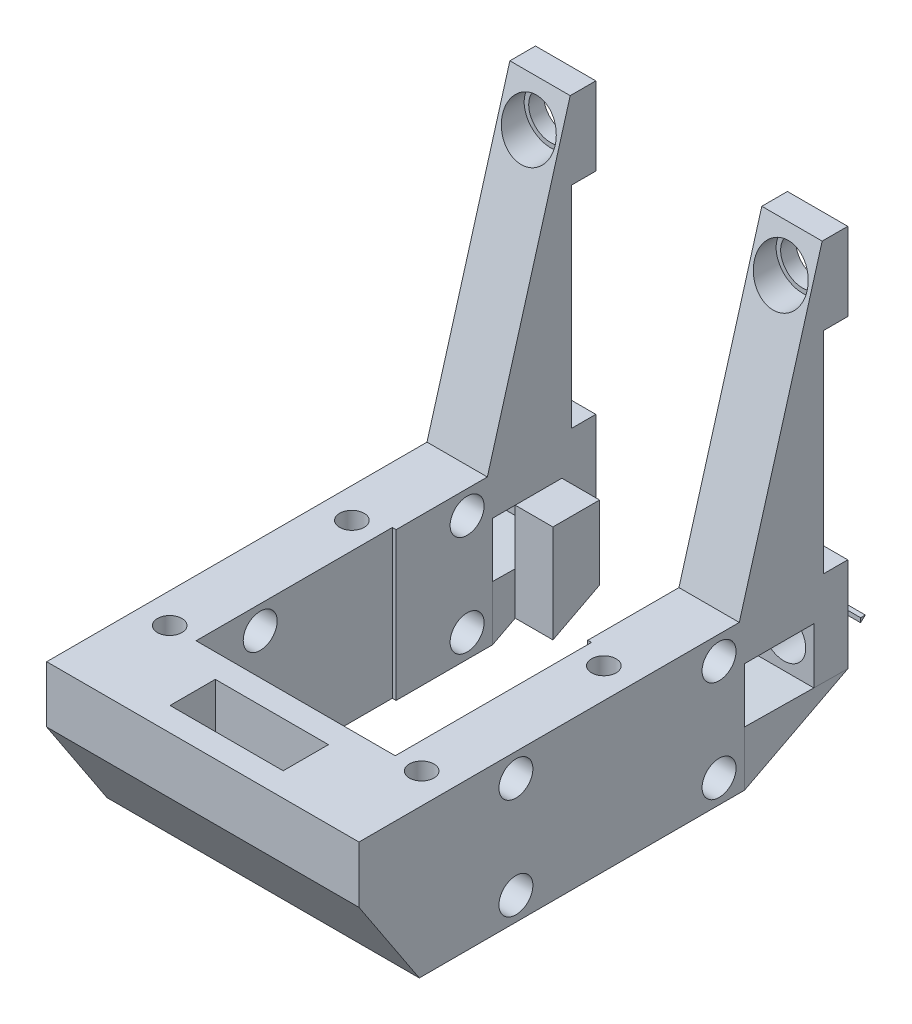
SolidWorks part; units mm, degrees
ref_plane "Front Plane" through (0, 0, 0) normal (0, 0, 1) x (1, 0, 0)
ref_plane "Top Plane" through (0, 0, 0) normal (0, 1, 0) x (1, 0, 0)
ref_plane "Right Plane" through (0, 0, 0) normal (1, 0, 0) x (0, 0, -1)
sketch "Sketch1" plane through (-474.147, -1016.1135, 5527.2949) normal (0, 0, 1) x (1, 0, 0)
  line L1 (211.6017, 683.0822) -> (219.1017, 683.0822)
  line L2 (211.6017, 683.0822) -> (211.6017, 675.5822)
  line L3 (211.6017, 675.5822) -> (219.1017, 675.5822)
  line L4 (219.1017, 683.0822) -> (219.1017, 675.5822)
  line L6 (237.0017, 683.0822) -> (237.0017, 675.5822)
  line L7 (237.0017, 675.5822) -> (229.5017, 675.5822)
  line L8 (229.5017, 683.0822) -> (229.5017, 675.5822)
  line L9 (237.0017, 683.0822) -> (229.5017, 683.0822)
  line L10 (237.0017, 718.5082) -> (229.5017, 718.5082)
  line L11 (237.0017, 711.0082) -> (237.0017, 718.5082)
  line L12 (229.5017, 711.0082) -> (229.5017, 718.5082)
  line L13 (237.0017, 711.0082) -> (229.5017, 711.0082)
  line L14 (211.6017, 718.5082) -> (219.1017, 718.5082)
  line L15 (211.6017, 711.0082) -> (211.6017, 718.5082)
  line L16 (219.1017, 711.0082) -> (219.1017, 718.5082)
  line L17 (211.6017, 711.0082) -> (219.1017, 711.0082)
  line L18 (219.1017, 675.5822) -> (229.5017, 675.5822) construction
  line L20 (237.0017, 683.0822) -> (237.0017, 711.0082) construction
  line L22 (211.6017, 683.0822) -> (211.6017, 711.0082) construction
  line L24 (219.1017, 718.5082) -> (229.5017, 718.5082) construction
  dimension "D1" = 237.1453
  dimension "D2" = 244.6453
  dimension "D3" = 255.0453
  dimension "D4" = 297.6053
  dimension "D5" = 333.0313
extrude "Boss-Extrude1" add sketch "Sketch1" along normal blind 5.5
sketch "Sketch2" plane through (0, 0, 5532.7949) normal (0, 0, 1) x (1, 0, 0)
  line L0 (-229.1453, -333.0313) -> (-229.1453, -340.5313)
  line L1 (-262.5453, -333.0313) -> (-270.5453, -333.0313)
  line L2 (-262.5453, -333.0313) -> (-262.5453, -340.5313)
  line L3 (-262.5453, -340.5313) -> (-270.5453, -340.5313)
  line L4 (-270.5453, -333.0313) -> (-270.5453, -340.5313)
  line L5 (-262.5453, -333.0313) -> (-262.5453, -340.5313) construction
  line L6 (-262.5453, -340.5313) -> (-255.0453, -340.5313) construction
  line L7 (-249.8453, -297.6053) -> (-249.8453, -340.5313) construction
  line L8 (-262.5453, -319.0683) -> (-237.1453, -319.0683) construction
  line L9 (-237.1453, -340.5313) -> (-229.1453, -340.5313)
  line L10 (-237.1453, -333.0313) -> (-237.1453, -340.5313)
  line L11 (-237.1453, -333.0313) -> (-229.1453, -333.0313)
  dimension "D1" = 7.5
  dimension "D2" = 8
  dimension "D3" = 12.7
  dimension "D4" = 21.463
extrude "Boss-Extrude2" add sketch "Sketch2" along normal blind 45 and the other way blind 5.5
sketch "Sketch3" plane through (0, 0, 5577.7949) normal (0, 0, 1) x (1, 0, 0)
  line L0 (-237.1453, -340.5313) -> (-229.1453, -340.5313) construction
  line L1 (-270.5453, -333.0313) -> (-229.1453, -333.0313)
  line L2 (-270.5453, -333.0313) -> (-270.5453, -340.5313)
  line L3 (-270.5453, -340.5313) -> (-229.1453, -340.5313)
  line L4 (-229.1453, -333.0313) -> (-229.1453, -340.5313)
  line L5 (-229.1453, -340.5313) -> (-229.1453, -333.0313) construction
extrude "Boss-Extrude3" add sketch "Sketch3" along normal blind 16
sketch "Sketch4" plane through (-262.5453, 0, 0) normal (-1, 0, 0) x (0, 0, 1)
  line L3 (5527.2949, -333.0313) -> (5527.2949, -294.744)
  line L4 (5527.2949, -294.744) -> (5532.3941, -294.744)
  line L5 (5527.2949, -297.6053) -> (5527.2949, -305.1053) construction
  line L6 (5532.3941, -294.744) -> (5543.3789, -333.0313)
  line L7 (5543.3789, -333.0313) -> (5527.2949, -333.0313)
  line L8 (5543.3789, -333.0313) -> (5581.4885, -333.0313) construction
extrude "Boss-Extrude4" add sketch "Sketch4" along normal blind 8
ref_plane "Plane1" through (-249.8453, 0, 0) normal (-1, 0, 0) x (0, 0, 1)
mirror "Mirror1" about plane through (-249.8453, 0, 0) normal (-1, 0, 0) of "Boss-Extrude2", "Boss-Extrude4"
sketch "Sketch5" plane through (0, 0, 5532.7949) normal (0, 0, 1) x (1, 0, 0)
  line L0 (-258.7953, -297.6053) -> (-258.7953, -305.1053) construction
  line L1 (-255.0453, -297.6053) -> (-262.5453, -297.6053) construction
  line L2 (-262.5453, -305.1053) -> (-255.0453, -305.1053) construction
  line L3 (-255.0453, -301.3553) -> (-262.5453, -301.3553) construction
  line L4 (-255.0453, -305.1053) -> (-255.0453, -297.6053) construction
  line L5 (-262.5453, -297.6053) -> (-262.5453, -305.1053) construction
  line L6 (-255.0453, -297.6053) -> (-244.6453, -297.6053) construction
  line L7 (-249.8453, -297.6053) -> (-249.8453, -305.1053) construction
  line L8 (-255.0453, -305.1053) -> (-244.6453, -305.1053) construction
  line L9 (-255.0453, -340.5313) -> (-244.6453, -340.5313) construction
  line L10 (-255.0453, -333.0313) -> (-244.6453, -333.0313) construction
  line L11 (-249.8453, -305.1053) -> (-249.8453, -333.0313) construction
  line L12 (-255.0453, -333.0313) -> (-255.0453, -305.1053) construction
  line L13 (-249.8453, -319.0683) -> (-255.0453, -319.0683) construction
  line L14 (-244.6453, -301.3553) -> (-237.1453, -301.3553) construction
  line L15 (-240.8953, -297.6053) -> (-240.8953, -305.1053) construction
  line L16 (-244.6453, -336.7813) -> (-237.1453, -336.7813) construction
  line L17 (-240.8953, -340.5313) -> (-240.8953, -333.0313) construction
  line L18 (-258.7953, -340.5313) -> (-258.7953, -333.0313) construction
  line L19 (-255.0453, -336.7813) -> (-262.5453, -336.7813) construction
  circle A0 centre (-258.7953, -301.3553) radius 2.5
  circle A1 centre (-240.8953, -301.3553) radius 2.5
  circle A2 centre (-240.8953, -336.7813) radius 2.5
  circle A3 centre (-258.7953, -336.7813) radius 2.5
  dimension "D1" = 5
extrude "Cut-Extrude1" cut sketch "Sketch5" against normal blind 8
sketch "Sketch6" plane through (-270.5453, 0, 0) normal (-1, 0, 0) x (0, 0, 1)
  line L0 (5527.2949, -340.5313) -> (5593.7949, -340.5313) construction
  line L1 (5539.6853, -340.5313) -> (5577.7949, -340.5313)
  line L2 (5539.6853, -340.5313) -> (5539.6853, -352.6436)
  line L3 (5539.6853, -352.6436) -> (5577.7949, -352.6436)
  line L4 (5577.7949, -340.5313) -> (5577.7949, -352.6436)
extrude "Boss-Extrude6" add sketch "Sketch6" against normal blind 8
ref_plane "Plane2" through (-249.8453, 0, 0) normal (-1, 0, 0) x (0, 0, 1)
mirror "Mirror2" about plane through (-249.8453, 0, 0) normal (-1, 0, 0) of "Boss-Extrude6"
sketch "Sketch9" plane through (0, 0, 5577.7949) normal (0, 0, 1) x (1, 0, 0)
  line L0 (-262.5453, -352.6436) -> (-270.5453, -352.6436) construction
  line L1 (-270.5453, -352.6436) -> (-229.1453, -352.6436)
  line L2 (-270.5453, -352.6436) -> (-270.5453, -340.5313)
  line L3 (-270.5453, -340.5313) -> (-229.1453, -340.5313)
  line L4 (-229.1453, -352.6436) -> (-229.1453, -340.5313)
  line L5 (-270.5453, -352.6436) -> (-270.5453, -340.5313) construction
  line L6 (-270.5453, -340.5313) -> (-229.1453, -340.5313) construction
extrude "Boss-Extrude7" add sketch "Sketch9" along normal blind 8
sketch "Sketch10" plane through (-270.5453, 0, 0) normal (-1, 0, 0) x (0, 0, 1)
  line L0 (5572.9896, -336.1377) -> (5572.9896, -333.0313) construction
  line L1 (5543.3789, -333.0313) -> (5593.7949, -333.0313) construction
  line L2 (5572.9896, -352.6436) -> (5572.9896, -349.5373) construction
  line L3 (5539.6853, -352.6436) -> (5585.7949, -352.6436) construction
  circle A4 centre (5546.0612, -349.5373) radius 2.25
  circle A5 centre (5572.9896, -349.5373) radius 2.25
  circle A6 centre (5546.0612, -336.1377) radius 2.25
  circle A7 centre (5572.9896, -336.1377) radius 2.25
  dimension "D1" = 4.5
  dimension "D2" = 13.6671
  dimension "D3" = 40.5955
  dimension "D4" = 3.1064
extrude "Cut-Extrude2" cut sketch "Sketch10" against normal through all
sketch "Sketch11" plane through (-270.5453, 0, 0) normal (-1, 0, 0) x (0, 0, 1)
  line L0 (5527.2949, -340.3725) -> (5539.6853, -352.6436)
  line L1 (5527.2949, -294.744) -> (5527.2949, -340.5313) construction
  line L2 (5539.6853, -340.5313) -> (5539.6853, -352.6436) construction
  line L3 (5539.6853, -352.6436) -> (5539.6853, -340.5313)
  line L4 (5527.2949, -340.5313) -> (5539.6853, -340.5313) construction
  line L5 (5539.6853, -340.5313) -> (5527.2949, -340.3725)
  line L7 (5539.6853, -352.6436) -> (5585.7949, -352.6436) construction
  dimension "D1" = 12.2712
extrude "Boss-Extrude8" add sketch "Sketch11" against normal blind 8
sketch "Sketch12" plane through (-229.1453, 0, 0) normal (1, 0, 0) x (0, 0, -1)
  line L0 (-5539.6853, -352.6436) -> (-5526.672, -340.5313)
  line L1 (-5539.6853, -340.5313) -> (-5539.6853, -352.6436) construction
  line L2 (-5539.6853, -340.5313) -> (-5527.2949, -340.5313) construction
  line L3 (-5526.672, -340.5313) -> (-5539.6853, -340.5313)
  line L4 (-5539.6853, -340.5313) -> (-5539.6853, -352.6436)
  line L5 (-5526.672, -340.341) -> (-5526.672, -300.7017) construction
extrude "Boss-Extrude9" add sketch "Sketch12" against normal blind 8
sketch "Sketch13" plane through (-270.5453, 0, 0) normal (-1, 0, 0) x (0, 0, 1)
  line L0 (5527.8316, -294.744) -> (5527.8316, -302.244) construction
  line L1 (5532.3941, -294.744) -> (5527.2949, -294.744) construction
  line L2 (5527.8316, -340.5313) -> (5527.8316, -333.0313) construction
  line L3 (5527.2949, -294.744) -> (5527.2949, -340.5313) construction
  line L4 (5527.2949, -333.0313) -> (5532.2204, -333.0313)
  line L5 (5527.2949, -333.0313) -> (5527.2949, -305.1053)
  line L6 (5527.2949, -305.1053) -> (5532.2204, -305.1053)
  line L7 (5532.2204, -333.0313) -> (5532.2204, -305.1053)
  dimension "D1" = 7.5
  dimension "D2" = 7.5
extrude "Cut-Extrude3" cut sketch "Sketch13" against normal through all
sketch "Sketch14" plane through (-270.5453, 0, 0) normal (-1, 0, 0) x (0, 0, 1)
  line L0 (5585.7949, -352.6436) -> (5593.7949, -340.5313)
  line L1 (5585.7949, -340.5313) -> (5585.7949, -352.6436) construction
  line L2 (5585.7949, -340.5313) -> (5593.7949, -340.5313) construction
  line L3 (5593.7949, -340.5313) -> (5585.7949, -340.5313)
  line L4 (5585.7949, -340.5313) -> (5585.7949, -352.6436)
extrude "Boss-Extrude10" add sketch "Sketch14" against normal blind 41.4
sketch "Sketch16" plane through (0, -333.0313, 0) normal (0, 1, 0) x (1, 0, 0)
  line L1 (-263.0453, -5555.4748) -> (-236.6453, -5555.4748)
  line L2 (-263.0453, -5555.4748) -> (-263.0453, -5581.4885)
  line L3 (-263.0453, -5581.4885) -> (-236.6453, -5581.4885)
  line L4 (-236.6453, -5555.4748) -> (-236.6453, -5581.4885)
  line L5 (-263.0453, -5566.5853) -> (-270.5453, -5566.5853) construction
  line L6 (-270.5453, -5543.3789) -> (-270.5453, -5593.7949) construction
  line L7 (-236.6453, -5567.7425) -> (-229.1453, -5567.7425) construction
  line L8 (-229.1453, -5593.7949) -> (-229.1453, -5543.3789) construction
  line L10 (-229.1453, -5543.3789) -> (-237.1453, -5543.3789) construction
  dimension "D1" = 7.5
  dimension "D2" = 12.0959
  dimension "D3" = 23.2064
  dimension "D4" = 24.3636
  dimension "D5" = 38.1096
extrude "Cut-Extrude5" cut sketch "Sketch16" against normal through all
sketch "Sketch17" plane through (0, -297.6053, 0) normal (0, 1, 0) x (1, 0, 0)
  line L1 (-237.1453, -5527.2949) -> (-262.5453, -5527.2949)
  line L2 (-237.1453, -5527.2949) -> (-237.1453, -5532.7949)
  line L3 (-237.1453, -5532.7949) -> (-262.5453, -5532.7949)
  line L4 (-262.5453, -5527.2949) -> (-262.5453, -5532.7949)
extrude "Cut-Extrude6" cut sketch "Sketch17" against normal blind 50
sketch "Sketch18" plane through (0, -294.744, 0) normal (0, 1, 0) x (1, 0, 0)
  line L1 (-270.5453, -5527.2949) -> (-229.1453, -5527.2949)
  line L2 (-270.5453, -5527.2949) -> (-270.5453, -5528.9982)
  line L3 (-270.5453, -5528.9982) -> (-229.1453, -5528.9982)
  line L4 (-229.1453, -5527.2949) -> (-229.1453, -5528.9982)
  line L5 (-229.1453, -5532.3941) -> (-229.1453, -5527.2949) construction
extrude "Cut-Extrude7" cut sketch "Sketch18" against normal blind 50
sketch "Sketch19" plane through (0, 0, 5528.9982) normal (0, 0, -1) x (-1, 0, 0)
  line L0 (233.1453, -294.744) -> (233.1453, -305.1053) construction
  line L1 (237.1453, -294.744) -> (229.1453, -294.744) construction
  line L2 (237.1453, -305.1053) -> (229.1453, -305.1053) construction
  line L3 (229.1453, -299.9246) -> (237.1453, -299.9246) construction
  line L4 (229.1453, -305.1053) -> (229.1453, -294.744) construction
  line L5 (237.1453, -305.1053) -> (237.1453, -294.744) construction
  circle A0 centre (233.1453, -299.9246) radius 2.9
  dimension "D1" = 5.8
extrude "Cut-Extrude8" cut sketch "Sketch19" against normal blind 50
ref_plane "Plane3" through (0, 0, 5538.9982) normal (0, 0, -1) x (-1, 0, 0)
sketch "Sketch20" plane through (0, 0, 5538.9982) normal (0, 0, -1) x (-1, 0, 0)
  circle A1 centre (233.1453, -299.9246) radius 3.5
  dimension "D1" = 7
extrude "Cut-Extrude9" cut sketch "Sketch20" along normal blind 8
ref_plane "Plane4" through (-249.8453, 0, 0) normal (-1, 0, 0) x (0, 0, 1)
mirror "Mirror3" about plane through (-249.8453, 0, 0) normal (-1, 0, 0) of "Cut-Extrude9", "Cut-Extrude8"
ref_plane "Plane5" through (0, -319.0683, 0) normal (0, 1, 0) x (1, 0, 0)
sketch "Sketch21" plane through (-270.5453, 0, 0) normal (-1, 0, 0) x (0, 0, 1)
  line L0 (5528.9982, -342.0594) -> (5528.9982, -333.0313) construction
  line L1 (5528.9982, -338.1154) -> (5539.6853, -338.1154)
  line L2 (5528.9982, -338.1154) -> (5528.9982, -352.6436)
  line L3 (5528.9982, -352.6436) -> (5539.6853, -352.6436)
  line L4 (5539.6853, -338.1154) -> (5539.6853, -352.6436)
extrude "Cut-Extrude10" cut sketch "Sketch21" against normal blind 55
sketch "Sketch22" plane through (0, -338.1154, 0) normal (0, -1, 0) x (1, 0, 0)
  line L0 (-262.5453, 5528.9982) -> (-262.5453, 5539.6853) construction
  line L1 (-270.5453, 5528.9982) -> (-262.5453, 5528.9982)
  line L2 (-270.5453, 5528.9982) -> (-270.5453, 5533.4982)
  line L3 (-270.5453, 5533.4982) -> (-262.5453, 5533.4982)
  line L4 (-262.5453, 5528.9982) -> (-262.5453, 5533.4982)
  dimension "D1" = 4.5
extrude "Boss-Extrude11" add sketch "Sketch22" along normal blind 7.4279
mirror "Mirror5" about plane through (-249.8453, 0, 0) normal (-1, 0, 0) of "Boss-Extrude11"
sketch "Sketch23" plane through (0, 0, 5528.9982) normal (0, 0, -1) x (-1, 0, 0)
  circle A0 centre (233.1189, -341.4699) radius 2.9
  dimension "D1" = 5.8
extrude "Cut-Extrude11" cut sketch "Sketch23" against normal blind 5
ref_plane "Plane6" through (-270.5453, -338.1154, 5539.6853) normal (0, 1, 0) x (1, 0, 0)
sketch "Sketch25" plane through (-262.5453, 0, 0) normal (1, 0, 0) x (0, 0, -1)
  line L0 (-5539.6853, -338.1154) -> (-5533.4982, -338.1154) construction
  line L1 (-5539.6853, -352.6436) -> (-5533.4982, -352.6436)
  line L2 (-5539.6853, -352.6436) -> (-5539.6853, -338.1154)
  line L3 (-5539.6853, -338.1154) -> (-5533.4982, -338.1154)
  line L4 (-5533.4982, -352.6436) -> (-5533.4982, -338.1154)
extrude "Boss-Extrude12" add sketch "Sketch25" along normal blind 5 separate body
sketch "Sketch26" plane through (-270.5453, 0, 0) normal (-1, 0, 0) x (0, 0, 1)
  line L0 (5539.6853, -352.6436) -> (5585.7949, -352.6436) construction
  line L1 (5539.6853, -338.1154) -> (5542.6853, -338.1154)
  line L2 (5539.6853, -338.1154) -> (5539.6853, -352.6436)
  line L3 (5539.6853, -352.6436) -> (5542.6853, -352.6436)
  line L4 (5542.6853, -338.1154) -> (5542.6853, -352.6436)
  dimension "D1" = 3
extrude "Cut-Extrude12" cut sketch "Sketch26" against normal through all
sketch "Sketch27" plane through (-270.5453, 0, 0) normal (-1, 0, 0) x (0, 0, 1)
  line L0 (5542.6853, -352.6436) -> (5528.9982, -345.5433)
  line L1 (5528.9982, -345.5433) -> (5542.6853, -345.3795)
  line L2 (5542.6853, -352.6436) -> (5542.6853, -338.1154) construction
  line L3 (5542.6853, -345.3795) -> (5542.6853, -352.6436)
extrude "Boss-Extrude15" add sketch "Sketch27" against normal up to surface (8 mm away) separate body up to face at (-262.5453, -345.3795, 5536.5917)
mirror "Mirror6" about plane through (-249.8453, 0, 0) normal (-1, 0, 0) of "Cut-Extrude11"
sketch "Sketch28" plane through (-262.5453, 0, 0) normal (-1, 0, 0) x (0, 0, 1)
  line L0 (5533.4982, -347.8777) -> (5539.6853, -351.0873)
  line L1 (5542.6853, -352.6436) -> (5528.9982, -345.5433) construction
  line L2 (5533.4982, -352.6436) -> (5533.4982, -338.1154) construction
  line L3 (5539.6853, -338.1154) -> (5539.6853, -352.6436) construction
  line L4 (5539.6853, -351.0873) -> (5543.3789, -359.5636)
  line L5 (5543.3789, -377.1583) -> (5543.3789, -333.0313) construction
  line L6 (5543.3789, -359.5636) -> (5533.2622, -359.5636)
  line L7 (5533.2622, -359.5636) -> (5533.4982, -347.8777)
extrude "Cut-Extrude13" cut sketch "Sketch28" against normal through all
mirror "Mirror11" about plane through (-249.8453, 0, 0) normal (-1, 0, 0) of bodies 170 168
sketch "Sketch29" plane through (0, -333.0313, 0) normal (0, 1, 0) x (1, 0, 0)
  line L0 (-249.8453, -5593.7949) -> (-249.8453, -5581.4885) construction
  line L1 (-229.1453, -5593.7949) -> (-270.5453, -5593.7949) construction
  line L2 (-263.0453, -5581.4885) -> (-236.6453, -5581.4885) construction
  line L4 (-242.3453, -5584.6417) -> (-257.3453, -5584.6417)
  line L5 (-242.3453, -5584.6417) -> (-242.3453, -5590.6417)
  line L6 (-242.3453, -5590.6417) -> (-257.3453, -5590.6417)
  line L7 (-257.3453, -5584.6417) -> (-257.3453, -5590.6417)
  line L8 (-242.3453, -5584.6417) -> (-257.3453, -5590.6417) construction
  line L9 (-242.3453, -5590.6417) -> (-257.3453, -5584.6417) construction
  point P6 (-249.8453, -5587.6417)
  dimension "D1" = 15
  dimension "D2" = 6
extrude "Cut-Extrude14" cut sketch "Sketch29" against normal blind 10
sketch "Sketch30" plane through (0, -333.0313, 0) normal (0, 1, 0) x (1, 0, 0)
  line L0 (-270.5453, -5557.3356) -> (-266.5453, -5557.3356) construction
  line L1 (-270.5453, -5543.3789) -> (-270.5453, -5593.7949) construction
  line L2 (-266.5453, -5543.3789) -> (-266.5453, -5565.5846) construction
  line L3 (-270.5453, -5543.3789) -> (-262.5453, -5543.3789) construction
  circle A0 centre (-266.5453, -5557.3356) radius 1.625
  dimension "D1" = 3.25
extrude "Cut-Extrude15" cut sketch "Sketch30" against normal blind 10
sketch "Sketch31" plane through (0, -333.0313, 0) normal (0, 1, 0) x (1, 0, 0)
  line L0 (-229.1453, -5581.4885) -> (-234.0224, -5581.4885) construction
  line L1 (-229.1453, -5593.7949) -> (-229.1453, -5543.3789) construction
  line L2 (-263.0453, -5581.4885) -> (-236.6453, -5581.4885) construction
  line L3 (-233.1453, -5543.3789) -> (-233.1453, -5581.4885) construction
  line L4 (-229.1453, -5543.3789) -> (-237.1453, -5543.3789) construction
  circle A0 centre (-233.1453, -5581.4885) radius 1.625
  dimension "D1" = 3.25
extrude "Cut-Extrude16" cut sketch "Sketch31" against normal blind 10
ref_plane "Plane7" through (-249.8453, 0, 0) normal (-1, 0, 0) x (0, 0, 1)
mirror "Mirror12" about plane through (-249.8453, 0, 0) normal (-1, 0, 0) of "Cut-Extrude16", "Cut-Extrude15"
